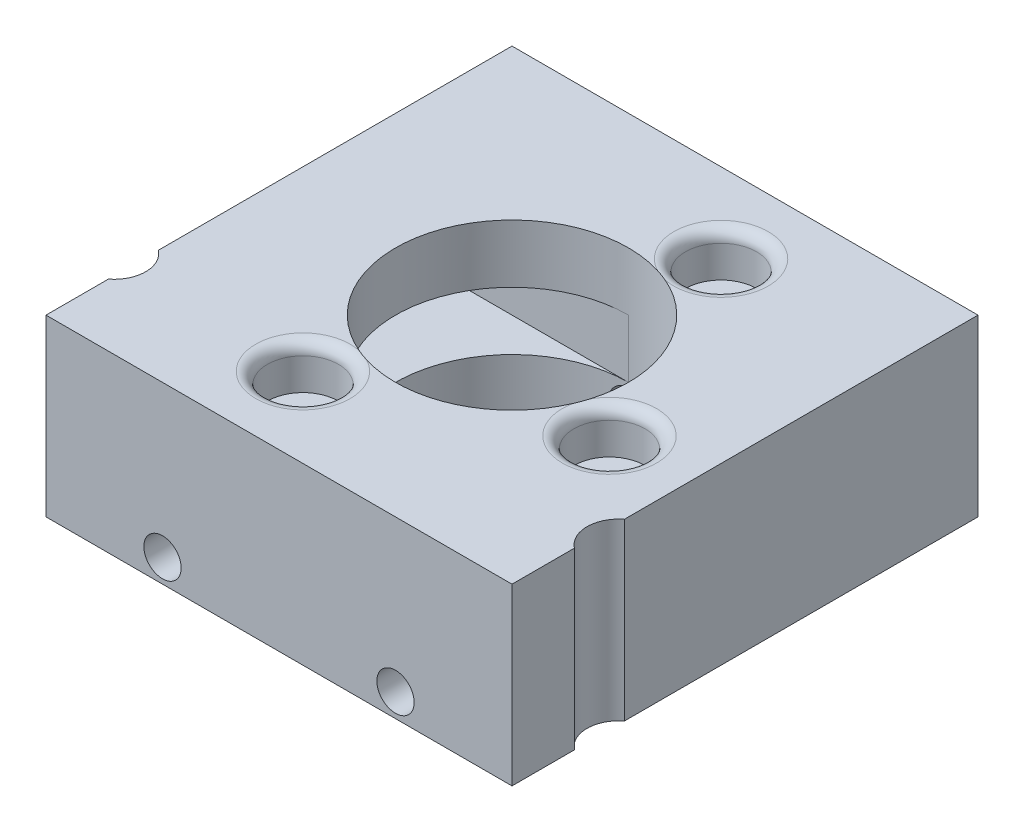
SolidWorks part; units mm, degrees
ref_plane "Front Plane" through (0, 0, 0) normal (0, 0, 1) x (1, 0, 0)
ref_plane "Top Plane" through (0, 0, 0) normal (0, 1, 0) x (1, 0, 0)
ref_plane "Right Plane" through (0, 0, 0) normal (1, 0, 0) x (0, 0, -1)
sketch "Sketch1" plane through (0, 0, 0) normal (0, 1, 0) x (1, 0, 0)
  line L0 (0, 0) -> (0, 35.4208) construction
  line L1 (-20, -20) -> (20, -20)
  line L2 (-20, -20) -> (-20, 20)
  line L3 (-20, 20) -> (20, 20)
  line L4 (20, -20) -> (20, 20)
  line L5 (-20, -20) -> (20, 20) construction
  line L6 (-20, 20) -> (20, -20) construction
  circle A0 centre (0, 0) radius 10
  circle A1 centre (0, 25) radius 2.7073
  circle A2 centre (21.6506, -12.5) radius 2.7073
  circle A3 centre (-21.6506, -12.5) radius 2.7073
  point P0 (0, 0)
  point P18 (0, 0)
  dimension "D2" = 20
  dimension "D1" = 25
  dimension "D3" = 40
  dimension "D4" = 40
  dimension "D5" = 3
extrude "Boss-Extrude1" add sketch "Sketch1" along normal blind 15 contours A3 L2 L1 L4 A2 L3 A0 region at (-19.4343, 0, 17.3229)
sketch "Sketch5" plane through (0, 0, 0) normal (1, 0, 0) x (0, 0, -1)
  line L0 (4.8229, 15) -> (-4.8229, 0) construction
  line L1 (10, 5) -> (-10, 5)
  line L2 (10, 5) -> (10, 10)
  line L3 (10, 10) -> (-10, 10)
  line L4 (-10, 5) -> (-10, 10)
  line L5 (10, 5) -> (-10, 10) construction
  line L6 (10, 10) -> (-10, 5) construction
  line L7 (20, 7.5) -> (-20, 7.5) construction
  line L8 (20, 15) -> (20, 0) construction
  line L9 (-20, 15) -> (-20, 0) construction
  line L10 (-10.3541, 15) -> (20, 15) construction
  line L11 (-10.3541, 0) -> (20, 0) construction
  point P0 (0, 7.5)
  dimension "D1" = 20
  dimension "D2" = 5
extrude "Square side-insert" cut sketch "Sketch5" against normal up to surface (20 mm away) up to face at (-20, 7.5, -4.8229)
sketch "Sketch3" plane through (0, 0, -20) normal (0, 0, -1) x (-1, 0, 0)
  line L3 (0, 15) -> (0, 3) construction
  line L4 (20, 15) -> (-20, 15) construction
  circle A0 centre (0, 3) radius 1.6
  dimension "D2" = 3.2
  dimension "D1" = 12
extrude "Single Screw" cut sketch "Sketch3" against normal blind 17
sketch "Sketch2" plane through (0, 0, 20) normal (0, 0, 1) x (1, 0, 0)
  line L0 (0, 27.8717) -> (0, -11.9207) construction
  line L1 (20, 2) -> (10, 2)
  line L3 (10, 2) -> (10, 0)
  line L4 (-20, 0) -> (20, 0) construction
  line L5 (20, 15) -> (20, 0) construction
  circle A0 centre (10, 2) radius 1.6
  circle A1 centre (-10, 2) radius 1.6
  dimension "D3" = 3.2
  dimension "D1" = 10
  dimension "D2" = 2
extrude "Double Screw" cut sketch "Sketch2" against normal blind 10 contours A1 | A0
sketch "Sketch6" plane through (0, 15, 0) normal (0, 1, 0) x (1, 0, 0)
  line L0 (9.3969, -3.4202) -> (13.1557, -4.7883) construction
  line L1 (0, 0) -> (32.6244, 0) construction
  circle A0 centre (0, 0) radius 10 construction
  circle A1 centre (13.1557, -4.7883) radius 1.55
  circle A2 centre (-4.7883, -13.1557) radius 1.55
  circle A3 centre (-13.1557, 4.7883) radius 1.55 construction
  circle A4 centre (4.7883, 13.1557) radius 1.55
  circle A5 centre (13.1557, -4.7883) radius 3.05
  circle A6 centre (-4.7883, -13.1557) radius 3.05
  circle A7 centre (-13.1557, 4.7883) radius 3.05 construction
  circle A8 centre (4.7883, 13.1557) radius 3.05
  point P16 (0, 0)
  point P25 (0, 0)
  dimension "D2" = 3.1
  dimension "D1" = 4
  dimension "D6" = 20
  dimension "D4" = 1.5
  dimension "D3" = 4
  dimension "D5" = 4
extrude "Holes on 20 degree offset " cut sketch "Sketch6" against normal up to surface (15 mm away) contours A4 | A1 | A2 region at (13.1557, 15, 4.7883) region at (-4.7883, 15, 13.1557) region at (4.7883, 15, -13.1557) up to face at (0, 0, 6.25)
extrude "Cut-Extrude2" cut sketch "Sketch6<3>" against normal blind 3.7326 contours A8 A4 | A5 A1 | A6 A2 region at (10.192, 15, 4.7883) region at (-7.752, 15, 13.1557) region at (1.8245, 15, -13.1557)
sketch "Sketch6<3>" plane through (0, 15, 0) normal (0, 1, 0) x (1, 0, 0) same geometry as "Sketch6"
fillet "Fillet1" radius 1 3 edges at (4.7883, 15, -10.1057) (-4.7883, 15, 16.2057) (13.1557, 15, 7.8383)
